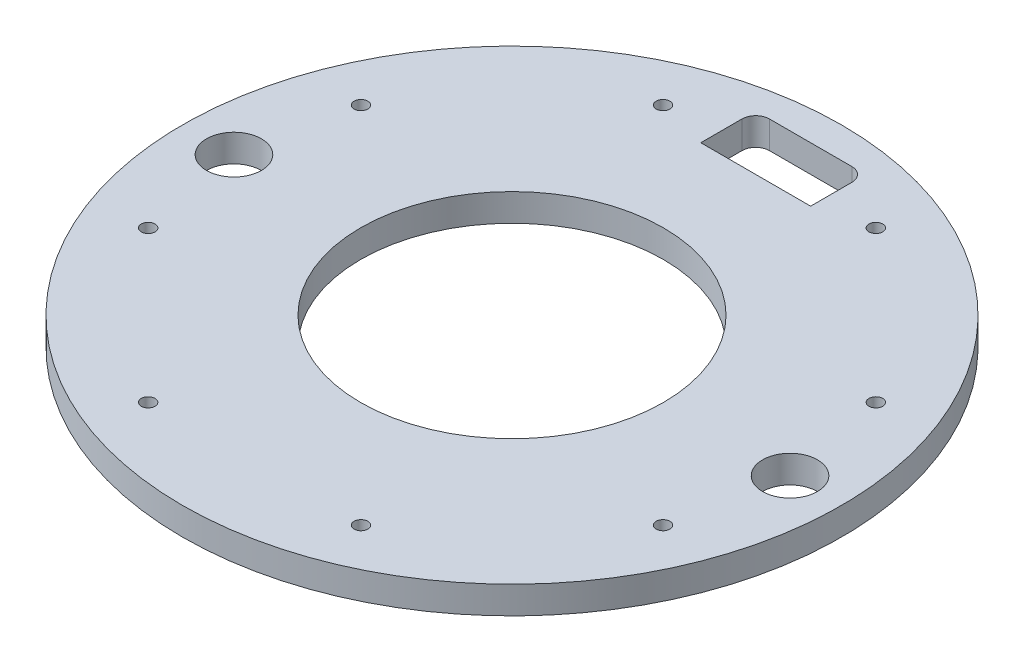
SolidWorks part; units mm, degrees
ref_plane "Front Plane" through (0, 0, 0) normal (0, 0, 1) x (1, 0, 0)
ref_plane "Top Plane" through (0, 0, 0) normal (0, 1, 0) x (1, 0, 0)
ref_plane "Right Plane" through (0, 0, 0) normal (1, 0, 0) x (0, 0, -1)
sketch "Sketch1" plane through (0, 0, 0) normal (0, 1, 0) x (1, 0, 0)
  circle A0 centre (0, 0) radius 76.2
  dimension "D1" = 152.4
extrude "Boss-Extrude1" add sketch "Sketch1" along normal blind 6.35
sketch "Sketch2" plane through (0, 6.35, 0) normal (0, 1, 0) x (1, 0, 0)
  circle A0 centre (0, 0) radius 35
  dimension "D1" = 70
extrude "Cut-Extrude1" cut sketch "Sketch2" against normal blind 6.35
sketch "Sketch3" plane through (0, 6.35, 0) normal (0, 1, 0) x (1, 0, 0)
  line L0 (-76.2, 0) -> (76.2, 0) construction
  line L1 (-51.5875, 51.5875) -> (51.5875, 51.5875) construction
  line L2 (-51.5875, 51.5875) -> (-51.5875, -51.5875) construction
  line L3 (-51.5875, -51.5875) -> (51.5875, -51.5875) construction
  line L4 (51.5875, 51.5875) -> (51.5875, -51.5875) construction
  circle A0 centre (0, 0) radius 76.2 construction
  circle A1 centre (-64.2875, 0) radius 6.35
  circle A2 centre (64.2875, 0) radius 6.35
  dimension "D1" = 12.7
  dimension "D2" = 12.7
  dimension "D3" = 12.7
  dimension "D4" = 12.7
extrude "Cut-Extrude2" cut sketch "Sketch3" against normal blind 10
sketch "Sketch4" plane through (0, 6.35, 0) normal (0, 1, 0) x (1, 0, 0)
  line L1 (50, -50) -> (-50, -50) construction
  line L2 (50, -50) -> (50, 50) construction
  line L3 (50, 50) -> (-50, 50) construction
  line L4 (-50, -50) -> (-50, 50) construction
  line L5 (50, -50) -> (-50, 50) construction
  line L6 (50, 50) -> (-50, -50) construction
  point P0 (0, 0)
  dimension "D1" = 100
  dimension "D2" = 100
sketch "Sketch5" plane through (0, 6.35, 0) normal (0, 1, 0) x (1, 0, 0)
  line L0 (-50, 24.6) -> (-59.525, 24.6) construction
  line L1 (-50, -50) -> (-50, 50) construction
  line L2 (-50, -24.6) -> (-59.525, -24.6) construction
  line L3 (50, 50) -> (-50, 50) construction
  line L4 (50, -50) -> (-50, -50) construction
  line L5 (-50, 50) -> (50, -50) construction
  line L6 (-50, -50) -> (50, 50) construction
  line L7 (24.6, 50) -> (24.6, 59.525) construction
  line L8 (-50, 50) -> (50, 50) construction
  line L9 (-50, 50) -> (-50, -50) construction
  line L10 (-50, -50) -> (50, -50) construction
  line L11 (50, 50) -> (50, -50) construction
  line L12 (-24.6, 50) -> (-24.6, 59.525) construction
  line L13 (50, 24.6) -> (59.525, 24.6) construction
  line L14 (-24.6, -50) -> (-24.6, -59.525) construction
  line L15 (24.6, -50) -> (24.6, -59.525) construction
  line L16 (50, -24.6) -> (59.525, -24.6) construction
  dimension "D1" = 25.4
  dimension "D2" = 25.4
  dimension "D3" = 9.525
  dimension "D4" = 9.525
sketch "Sketch6" plane through (0, 6.35, 0) normal (0, 1, 0) x (1, 0, 0)
  line L0 (0, 0) -> (0, 76.2) construction
  line L2 (-12.7, 56.3499) -> (12.7, 56.3499)
  line L3 (-12.7, 56.3499) -> (-12.7, 69.0499)
  line L4 (-12.7, 69.0499) -> (12.7, 69.0499)
  line L5 (12.7, 56.3499) -> (12.7, 69.0499)
  line L6 (-12.7, 56.3499) -> (12.7, 69.0499) construction
  line L7 (-12.7, 69.0499) -> (12.7, 56.3499) construction
  circle A0 centre (0, 0) radius 76.2 construction
  point P5 (0, 62.6999)
  dimension "D1" = 69.0499
  dimension "D2" = 25.4
  dimension "D3" = 12.7
extrude "Cut-Extrude3" cut sketch "Sketch6" against normal blind 10
fillet "Fillet1" radius 3.175 2 edges at (-12.7, 3.175, -69.0499) (12.7, 3.175, -69.0499)
sketch "Sketch7" plane through (0, 6.35, 0) normal (0, 1, 0) x (1, 0, 0)
  line L0 (0, 0) -> (0, 76.2) construction
  line L1 (0, 0) -> (53.8815, 53.8815) construction
  line L2 (0, 59.5249) -> (-24.5999, 59.5249) construction
  line L3 (0, 0) -> (76.2, 0) construction
  line L4 (0, -59.5249) -> (-24.5999, -59.5249) construction
  circle A0 centre (0, 0) radius 76.2 construction
  circle A1 centre (-24.5999, 59.5249) radius 1.5875
  circle A2 centre (24.5999, 59.5249) radius 1.5875
  circle A3 centre (24.5999, -59.5249) radius 1.5875
  circle A4 centre (-24.5999, -59.5249) radius 1.5875
  circle A5 centre (-59.5249, 24.5999) radius 1.5875
  circle A6 centre (-59.5249, -24.5999) radius 1.5875
  circle A7 centre (59.5249, 24.5999) radius 1.5875
  circle A8 centre (59.5249, -24.5999) radius 1.5875
  dimension "D1" = 45
  dimension "D2" = 59.5249
  dimension "D3" = 24.5999
extrude "Cut-Extrude4" cut sketch "Sketch7" against normal blind 10
